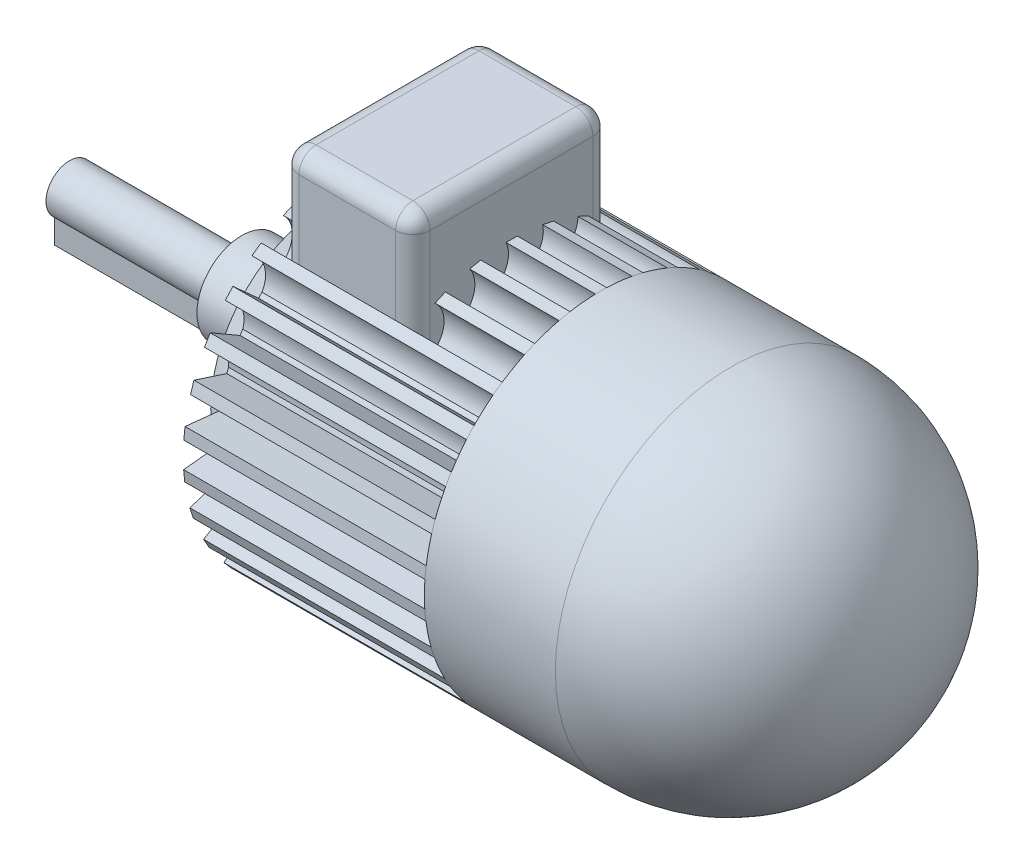
SolidWorks part; units mm, degrees
ref_plane "Front Plane" through (0, 0, 0) normal (0, 0, 1) x (1, 0, 0)
ref_plane "Top Plane" through (0, 0, 0) normal (0, 1, 0) x (1, 0, 0)
ref_plane "Right Plane" through (0, 0, 0) normal (1, 0, 0) x (0, 0, -1)
sketch "Sketch1" plane through (0, 0, 0) normal (0, 0, 1) x (1, 0, 0)
  line L0 (0, 0) -> (192, 0) construction
  line L1 (0, 0) -> (0, 13)
  line L2 (0, 13) -> (26, 13)
  line L3 (26, 13) -> (26, 35)
  line L8 (0, 0) -> (192, 0)
  line L9 (26, 35) -> (34.0097, 40.987)
  line L10 (34.0097, 40.987) -> (104.0097, 40.987)
  line L11 (104.0097, 40.987) -> (104.0097, 50.987)
  line L12 (104.0097, 50.987) -> (142.0097, 50.987)
  arc A2 (142.0097, 50.987) -> (192, 0) centre (142.0097, 0.987) cw
  dimension "D7" = 38
  dimension "D9" = 50
  dimension "D1" = 13
  dimension "D2" = 26
  dimension "D3" = 22
  dimension "D4" = 10
  dimension "D5" = 10
  dimension "D6" = 70
  dimension "D8" = 192
revolve "Revolve2" add sketch "Sketch1" angle 360 about L0
sketch "Sketch3" plane through (104.0097, 0, 0) normal (-1, 0, 0) x (0, 0, 1)
  line L0 (-1.9256, 40.9417) -> (-1.9256, 50.9506)
  line L1 (-1.9256, 50.9506) -> (1.3393, 50.9694)
  circle A2 centre (0, 0) radius 40.987 construction
  circle A3 centre (0, 0) radius 50.987 construction
  arc A4 (1.3393, 50.9694) -> (5.2145, 40.6539) centre (8.4346, 47.7492) ccw
  arc A5 (5.2145, 40.6539) -> (-1.9256, 40.9417) centre (0, 0) ccw
extrude "Boss-Extrude2" add sketch "Sketch3" along normal blind 70
pattern_circular "CirPattern2" count 30 over 360 about axis through (34.0097, 0, 0) along (-1, 0, 0) of "Boss-Extrude2"
ref_plane "Plane1" through (0, 70, 0) normal (0, 1, 0) x (1, 0, 0)
sketch "Sketch4" plane through (0, 70, 0) normal (0, 1, 0) x (1, 0, 0)
  line L0 (34.0097, 28.8755) -> (104.0097, 28.8755) construction
  line L1 (78.063, 28.8755) -> (39.9971, 28.8755)
  line L2 (78.063, 28.8755) -> (78.063, -28.3902)
  line L3 (78.063, -28.3902) -> (39.9971, -28.3902)
  line L4 (39.9971, 28.8755) -> (39.9971, -28.3902)
  line L5 (78.063, 28.8755) -> (39.9971, -28.3902) construction
  line L6 (78.063, -28.3902) -> (39.9971, 28.8755) construction
  line L7 (34.0097, -28.3902) -> (104.0097, -28.3902) construction
  point P4 (59.03, 0.2427)
extrude "Boss-Extrude3" add sketch "Sketch4" against normal up to next
fillet "Fillet1" radius 5 8 edges at (78.063, 56.0112, -28.8755) (39.9971, 56.0112, -28.8755) (59.03, 70, -28.8755) (78.063, 70, -0.2427) (39.9971, 70, -0.2427) (78.063, 56.1759, 28.3902) (39.9971, 56.1759, 28.3902) (59.03, 70, 28.3902)
sketch "Sketch6" plane through (0, 0, 0) normal (-1, 0, 0) x (0, 0, 1)
  circle A0 centre (0, 0) radius 6.8098
extrude "Boss-Extrude4" add sketch "Sketch6" along normal blind 50
sketch "Sketch7" plane through (-50, 0, 0) normal (-1, 0, 0) x (0, 0, 1)
  line L1 (4.3177, -5.266) -> (-4.3177, -5.266)
  line L2 (4.3177, -5.266) -> (4.3177, -12.262)
  line L3 (4.3177, -12.262) -> (-4.3177, -12.262)
  line L4 (-4.3177, -5.266) -> (-4.3177, -12.262)
  line L5 (4.3177, -5.266) -> (-4.3177, -12.262) construction
  line L6 (4.3177, -12.262) -> (-4.3177, -5.266) construction
  circle A0 centre (0, 0) radius 6.8098 construction
  circle A1 centre (0, 0) radius 13 construction
  point P4 (0, -8.764)
extrude "Boss-Extrude5" add sketch "Sketch7" against normal up to next
